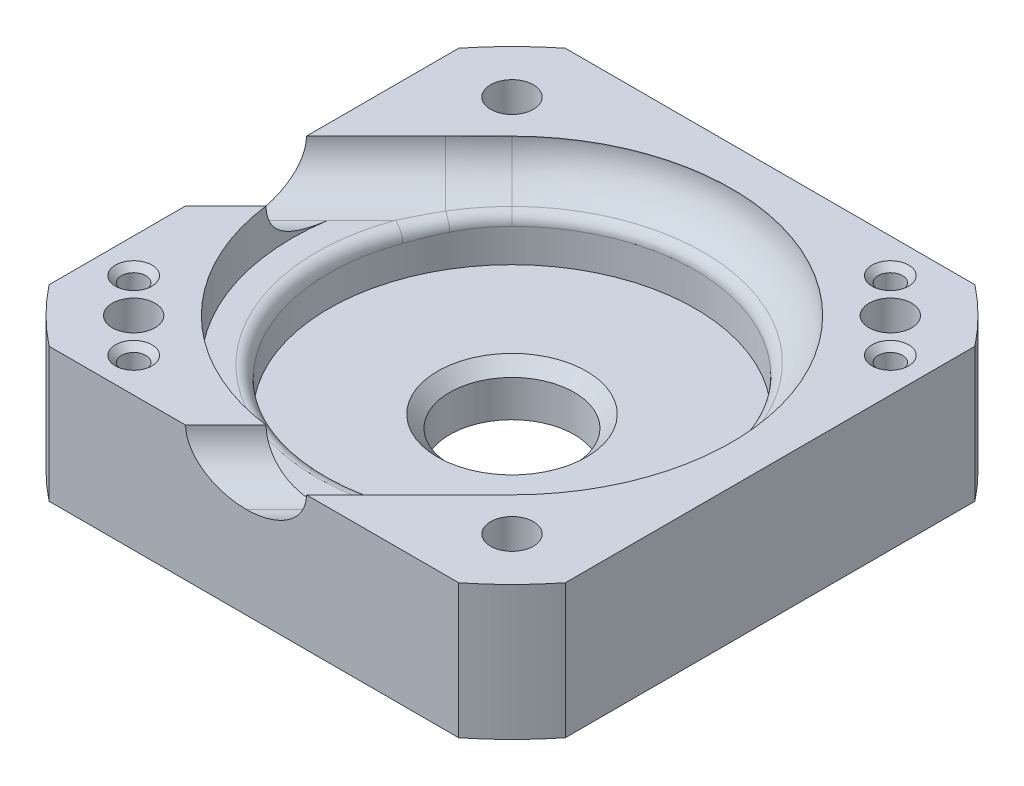
SolidWorks part; units mm, degrees
ref_plane "Front Plane" through (0, 0, 0) normal (0, 0, 1) x (1, 0, 0)
ref_plane "Top Plane" through (0, 0, 0) normal (0, 1, 0) x (1, 0, 0)
ref_plane "Right Plane" through (0, 0, 0) normal (1, 0, 0) x (0, 0, -1)
sketch "Sketch2" plane through (0, 0, 0) normal (0, 1, 0) x (1, 0, 0)
  line L1 (-21.15, 21.15) -> (21.15, 21.15)
  line L2 (-21.15, 21.15) -> (-21.15, -21.15)
  line L3 (-21.15, -21.15) -> (21.15, -21.15)
  line L4 (21.15, 21.15) -> (21.15, -21.15)
  line L5 (-21.15, 21.15) -> (21.15, -21.15) construction
  line L6 (-21.15, -21.15) -> (21.15, 21.15) construction
  point P0 (0, 0)
  dimension "D1" = 42.3
extrude "Boss-Extrude1" add sketch "Sketch2" along normal blind 11
sketch "Sketch3" plane through (0, 11, 0) normal (0, 1, 0) x (1, 0, 0)
  circle A0 centre (0, 0) radius 3
  dimension "D1" = 6
extrude "Cut-Extrude1" cut sketch "Sketch3" against normal through all
sketch "Sketch4" plane through (0, 11, 0) normal (0, 1, 0) x (1, 0, 0)
  line L1 (-15.5, 15.5) -> (15.5, 15.5) construction
  line L2 (-15.5, 15.5) -> (-15.5, -15.5) construction
  line L3 (-15.5, -15.5) -> (15.5, -15.5) construction
  line L4 (15.5, 15.5) -> (15.5, -15.5) construction
  line L5 (-15.5, 15.5) -> (15.5, -15.5) construction
  line L6 (-15.5, -15.5) -> (15.5, 15.5) construction
  circle A0 centre (-15.5, 15.5) radius 1.75
  circle A1 centre (15.5, 15.5) radius 1.75
  circle A2 centre (15.5, -15.5) radius 1.75
  circle A3 centre (-15.5, -15.5) radius 1.75
  point P0 (0, 0)
  point P16 (0, 0)
  dimension "D3" = 3.5
  dimension "D1" = 31
  dimension "D2" = 31
  dimension "D4" = 4
extrude "Cut-Extrude2" cut sketch "Sketch4" against normal through all
sketch "Sketch5" plane through (0, 11, 0) normal (0, 1, 0) x (1, 0, 0)
  circle A0 centre (0, 0) radius 27
  circle A1 centre (0, 0) radius 29.9106
  dimension "D1" = 54
extrude "Cut-Extrude4" cut sketch "Sketch5" against normal through all
sketch "Sketch6" plane through (0, 11, 0) normal (0, 1, 0) x (1, 0, 0)
  line L0 (-21.15, 4.3058) -> (-12.7279, 12.7279)
  line L1 (12.7279, -12.7279) -> (4.3058, -21.15)
  line L9 (-21.15, 16.7833) -> (-21.15, -16.7833) construction
  line L10 (-16.7833, -21.15) -> (16.7833, -21.15) construction
  line L11 (-7.7782, 7.7782) -> (-21.15, -5.5937) construction
  line L12 (4.3058, 21.15) -> (21.15, 4.3058) construction
  line L13 (7.3751, 21.15) -> (21.15, 7.3751) construction
  line L14 (16.7833, 21.15) -> (-16.7833, 21.15) construction
  line L15 (21.15, -16.7833) -> (21.15, 16.7833) construction
  line L18 (7.7782, -7.7782) -> (-5.5937, -21.15) construction
  line L19 (-21.15, 4.3058) -> (-21.15, -5.5937)
  line L21 (-2.2965, -17.8529) -> (-5.5937, -21.15)
  line L22 (-5.5937, -21.15) -> (4.3058, -21.15)
  line L23 (-17.8529, -2.2965) -> (-21.15, -5.5937)
  arc A0 (-12.7279, 12.7279) -> (12.7279, -12.7279) centre (0, 0) cw
  arc A2 (-17.8529, -2.2965) -> (-2.2965, -17.8529) centre (0, 0) ccw
  circle A3 centre (0, 0) radius 11 construction
  circle A5 centre (15.5, 15.5) radius 1.75 construction
  arc A6 (12.7279, -12.7279) -> (-12.7279, 12.7279) centre (0, 0) ccw
  circle M13 centre (0, 0) radius 3
  line M14 (-16.7833, -21.15) -> (16.7833, -21.15)
  line M20 (-21.15, 16.7833) -> (-21.15, -16.7833)
  dimension "D1" = 45
  dimension "D3" = 18
  dimension "D5" = 22
  dimension "D2" = 45
  dimension "D4" = 45
extrude "Cut-Extrude5" cut sketch "Sketch6" against normal offset from surface (7 mm away) 4 contours L23 A2 L21 L1 A0 L0 M14 M20 M13 region at (-16.5475, 11, -8.1254) up to face at (-15.5, 0, 17.25)
chamfer "Chamfer1" distance 1.8 angle 45 4 edges at (15.5, 0, -13.75) (-15.5, 0, -13.75) (-15.5, 0, 17.25) (15.5, 0, 17.25)
sketch "Sketch7" plane through (0, 4, 0) normal (0, 1, 0) x (1, 0, 0)
  circle A0 centre (0, 0) radius 5.1
  dimension "D1" = 10.2
extrude "Cut-Extrude6" cut sketch "Sketch7" against normal through all
sketch "Sketch8" plane through (0, 4, 0) normal (0, 1, 0) x (1, 0, 0)
  line L6 (-21.15, 4.3058) -> (-21.15, -5.5937)
  line L7 (-21.15, -5.5937) -> (-17.8529, -2.2965)
  line L8 (-2.2965, -17.8529) -> (-5.5937, -21.15)
  line L9 (-5.5937, -21.15) -> (4.3058, -21.15)
  line L10 (4.3058, -21.15) -> (12.7279, -12.7279)
  line L11 (-12.7279, 12.7279) -> (-21.15, 4.3058)
  line L12 (-21.15, 4.3058) -> (-21.15, -5.5937)
  line L13 (-21.15, -5.5937) -> (-17.8529, -2.2965)
  line L14 (-2.2965, -17.8529) -> (-5.5937, -21.15)
  line L15 (-5.5937, -21.15) -> (4.3058, -21.15)
  line L16 (4.3058, -21.15) -> (12.7279, -12.7279)
  line L17 (-12.7279, 12.7279) -> (-21.15, 4.3058)
  circle A0 centre (0, 0) radius 15
  arc A3 (-17.8529, -2.2965) -> (-2.2965, -17.8529) centre (0, 0) ccw
  arc A4 (12.7279, -12.7279) -> (-12.7279, 12.7279) centre (0, 0) ccw
  arc A5 (-17.8529, -2.2965) -> (-2.2965, -17.8529) centre (0, 0) ccw
  arc A6 (12.7279, -12.7279) -> (-12.7279, 12.7279) centre (0, 0) ccw
  dimension "D1" = 30
  dimension "D2" = 0
extrude "Boss-Extrude2" add sketch "Sketch8" along normal offset from surface (3.5 mm away) 3.5 up to face at (-15.5, 11, -13.75)
fillet "Fillet1" radius 3.5 4 edges at (8.5169, 7.5, 16.939) (-16.939, 7.5, -8.5169) (-19.5014, 7.5, 3.9451) (-3.9451, 7.5, 19.5014)
chamfer "Chamfer2" distance 1 angle 45 1 edges at (0, 4, 5.1)
fillet "Fillet2" radius 1 4 edges at (9.1485, 7.5, 11.8871) (-10.6066, 7.5, 10.6066) (-11.8871, 7.5, -9.1485) (10.6066, 7.5, -10.6066)
sketch "Sketch9" plane through (0, 11, 0) normal (0, 1, 0) x (1, 0, 0)
  line L0 (12.6716, 18.3284) -> (18.3284, 12.6716) construction
  line L1 (4.3058, -21.15) -> (16.7833, -21.15) construction
  line L2 (-19.0919, 19.0919) -> (19.0919, -19.0919) construction
  line L3 (-18.3284, -12.6716) -> (-12.6716, -18.3284) construction
  circle A0 centre (15.5, 15.5) radius 1.75 construction
  circle A1 centre (12.6716, 18.3284) radius 1
  circle A2 centre (18.3284, 12.6716) radius 1
  arc A3 (-16.7833, 21.15) -> (-21.15, 16.7833) centre (0, 0) ccw construction
  arc A4 (16.7833, -21.15) -> (21.15, -16.7833) centre (0, 0) ccw construction
  circle A5 centre (-12.6716, -18.3284) radius 1
  circle A6 centre (-18.3284, -12.6716) radius 1
  point P2 (15.5, 15.5)
  dimension "D2" = 2
  dimension "D3" = 2
  dimension "D1" = 4
  dimension "D4" = 45
extrude "Cut-Extrude7" cut sketch "Sketch9" against normal blind 3
chamfer "Chamfer3" distance 0.5 angle 45 4 edges at (12.6716, 11, -17.3284) (18.3284, 11, -11.6716) (-12.6716, 11, 17.3284) (-18.3284, 11, 11.6716)
